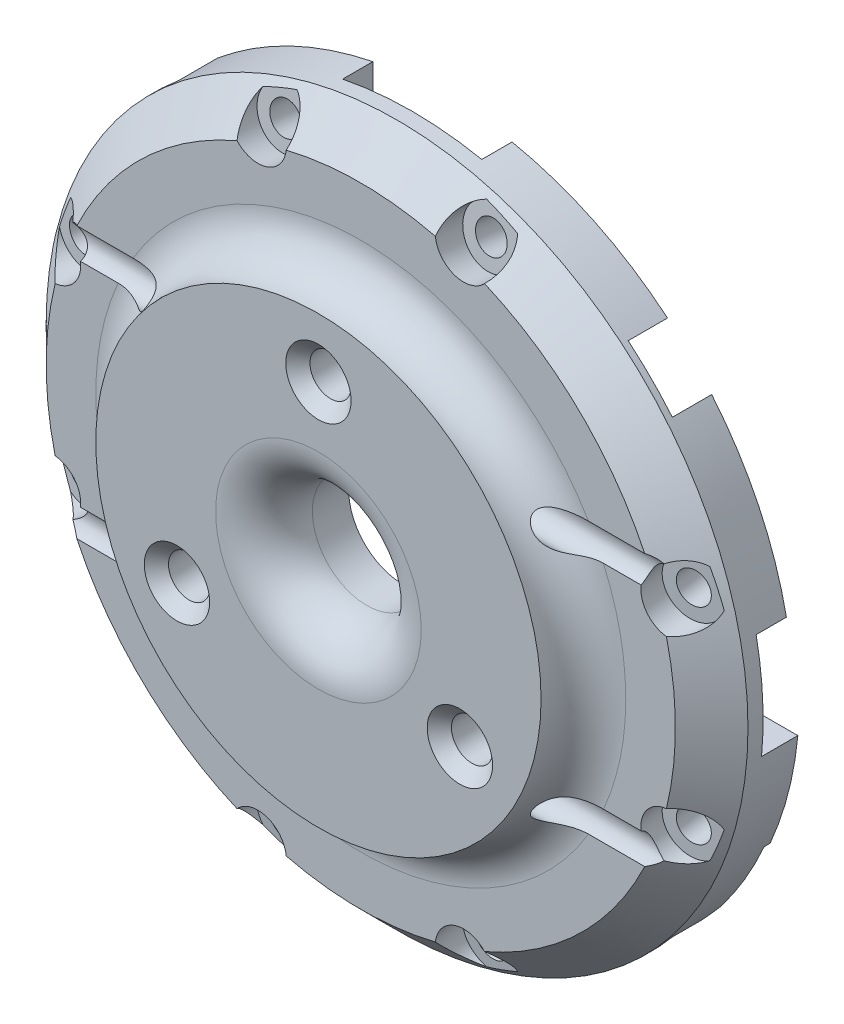
SolidWorks part; units mm, degrees
ref_plane "Front Plane" through (0, 0, 0) normal (0, 0, 1) x (1, 0, 0)
ref_plane "Top Plane" through (0, 0, 0) normal (0, 1, 0) x (1, 0, 0)
ref_plane "Right Plane" through (0, 0, 0) normal (1, 0, 0) x (0, 0, -1)
sketch "Sketch1" plane through (0, 0, 0) normal (0, 0, 1) x (1, 0, 0)
  circle A0 centre (0, 0) radius 29
  dimension "D1" = 58
extrude "Boss-Extrude1" add sketch "Sketch1" along normal blind 6.75
sketch "Sketch3" plane through (0, 0, 0) normal (0, 0, -1) x (-1, 0, 0)
  line L1 (-22.25, -22.25) -> (22.25, -22.25)
  line L2 (-22.25, -22.25) -> (-22.25, 22.25)
  line L3 (-22.25, 22.25) -> (22.25, 22.25)
  line L4 (22.25, -22.25) -> (22.25, 22.25)
  line L5 (-22.25, -22.25) -> (22.25, 22.25) construction
  line L6 (-22.25, 22.25) -> (22.25, -22.25) construction
  point P0 (0, 0)
  dimension "D1" = 44.5
extrude "Cut-Extrude1" cut sketch "Sketch3" against normal blind 3.25
sketch "Sketch4" plane through (0, 0, 6.75) normal (0, 0, 1) x (1, 0, 0)
  circle A0 centre (0, 0) radius 18.4
  dimension "D1" = 36.8
extrude "Boss-Extrude2" add sketch "Sketch4" along normal blind 3.5
fillet "Fillet1" radius 3.5 1 edges at (18.4, 0, 6.75)
sketch "Sketch5" plane through (0, 0, 10.25) normal (0, 0, 1) x (1, 0, 0)
  line L0 (-11.6913, -6.75) -> (0, 13.5) construction
  line L1 (0, 13.5) -> (11.6913, -6.75) construction
  line L2 (11.6913, -6.75) -> (-11.6913, -6.75) construction
  circle A2 centre (0, 0) radius 13.5 construction
  circle A3 centre (0, 13.5) radius 1.7
  circle A4 centre (11.6913, -6.75) radius 1.7
  circle A5 centre (-11.6913, -6.75) radius 1.7
  dimension "D1" = 3.4
  dimension "D2" = 27
extrude "Cut-Extrude2" cut sketch "Sketch5" against normal through all
sketch "Sketch7" plane through (0, 0, 3.25) normal (0, 0, -1) x (-1, 0, 0)
  circle A0 centre (-11.6913, -6.75) radius 3.25
  circle A1 centre (11.6913, -6.75) radius 3.25
  circle A2 centre (0, 13.5) radius 3.25
  dimension "D1" = 6.5
extrude "Cut-Extrude3" cut sketch "Sketch7" against normal blind 2
chamfer "Chamfer2" distance 3 angle 45 1 edges at (29, 0, 6.75)
sketch "Sketch9" plane through (0, 0, 0) normal (1, 0, 0) x (0, 0, -1)
  line L0 (-26.5723, 0) -> (15.7273, 0) construction
  line L2 (-6.75, 21.9) -> (-6.75, -21.9) construction
  circle A0 centre (-7.25, 10) radius 1.3
  circle A1 centre (-7.25, -10) radius 1.3
  dimension "D1" = 2.6
  dimension "D2" = 20
  dimension "D3" = 0.5
extrude "Cut-Extrude5" cut sketch "Sketch9" against normal through all both and the other way through all
sketch "Sketch10" plane through (0, 0, 0) normal (0, 0, -1) x (-1, 0, 0)
  line L0 (5.75, -22.0007) -> (5.75, -34.0342)
  line L1 (22.0007, 5.75) -> (34.0342, 5.75)
  line L2 (22.0007, 5.75) -> (22.0007, -5.75)
  line L3 (22.0007, -5.75) -> (34.0342, -5.75)
  line L4 (34.0342, 5.75) -> (34.0342, -5.75)
  line L5 (5.75, -22.0007) -> (-5.75, -22.0007)
  line L6 (-5.75, -22.0007) -> (-5.75, -34.0342)
  line L7 (5.75, -34.0342) -> (-5.75, -34.0342)
  line L8 (-22.0007, -5.75) -> (-34.0342, -5.75)
  line L9 (-22.0007, -5.75) -> (-22.0007, 5.75)
  line L10 (-22.0007, 5.75) -> (-34.0342, 5.75)
  line L11 (-34.0342, -5.75) -> (-34.0342, 5.75)
  line L12 (-5.75, 22.0007) -> (-5.75, 34.0342)
  line L13 (-5.75, 22.0007) -> (5.75, 22.0007)
  line L14 (5.75, 22.0007) -> (5.75, 34.0342)
  line L15 (-5.75, 34.0342) -> (5.75, 34.0342)
  point P4 (22.0007, 0)
  point P21 (0, 0)
  dimension "D1" = 11.5
  dimension "D2" = 4
extrude "Cut-Extrude6" cut sketch "Sketch10" against normal blind 2.5
sketch "Sketch13" plane through (0, 0, 3.25) normal (0, 0, -1) x (-1, 0, 0)
  line L0 (-22.25, 18.5994) -> (-22.25, -18.5994) construction
  line L1 (-22.15, 14.75) -> (-15.65, 14.75)
  line L2 (-22.15, 14.75) -> (-22.15, 8.25)
  line L3 (-22.15, 8.25) -> (-15.65, 8.25)
  line L4 (-15.65, 14.75) -> (-15.65, 8.25)
  line L5 (18.5994, 22.25) -> (-18.5994, 22.25) construction
  line L6 (14.75, 22.15) -> (14.75, 15.65)
  line L7 (14.75, 22.15) -> (8.25, 22.15)
  line L8 (8.25, 22.15) -> (8.25, 15.65)
  line L9 (14.75, 15.65) -> (8.25, 15.65)
  line L10 (22.15, -14.75) -> (15.65, -14.75)
  line L11 (22.15, -14.75) -> (22.15, -8.25)
  line L12 (22.15, -8.25) -> (15.65, -8.25)
  line L13 (15.65, -14.75) -> (15.65, -8.25)
  line L14 (-14.75, -22.15) -> (-14.75, -15.65)
  line L15 (-14.75, -22.15) -> (-8.25, -22.15)
  line L16 (-8.25, -22.15) -> (-8.25, -15.65)
  line L17 (-14.75, -15.65) -> (-8.25, -15.65)
  point P23 (0, 0)
  dimension "D1" = 0.1
  dimension "D2" = 7.5
  dimension "D4" = 6.5
  dimension "D3" = 4
extrude "Cut-Extrude9" cut sketch "Sketch13" against normal blind 2.25
chamfer "Chamfer5" distance 1 angle 45 12 edges at (-14.75, 18.9, 3.25) (-11.5, 15.65, 3.25) (-8.25, 18.9, 3.25) (14.75, -18.9, 3.25) (11.5, -15.65, 3.25) (8.25, -18.9, 3.25) (-18.9, -8.25, 3.25) (-15.65, -11.5, 3.25) (-18.9, -14.75, 3.25) (18.9, 8.25, 3.25) (15.65, 11.5, 3.25) (18.9, 14.75, 3.25)
sketch "Sketch14" plane through (0, 0, 0) normal (0, 0, -1) x (-1, 0, 0)
  line L1 (-35.1198, 0) -> (-19.2322, 0)
  line L2 (-35.1198, 0) -> (-35.1198, -11.6)
  line L3 (-35.1198, -11.6) -> (-19.2322, -11.6)
  line L4 (-19.2322, 0) -> (-19.2322, -11.6)
  dimension "D1" = 11.6
extrude "Cut-Extrude10" cut sketch "Sketch14" against normal up to surface (2.5 mm away) up to face at (25.4811, 0, 2.5)
fillet "Fillet2" radius 1.5 3 edges at (-8.5776, -5.8189, 3.25) (8.4413, -6.75, 3.25) (-3.25, 13.5, 3.25)
sketch "Sketch15" plane through (0, 0, 6.75) normal (0, 0, 1) x (1, 0, 0)
  line L0 (0, 0) -> (11.6673, 11.6673) construction
  line L1 (0, 0) -> (36.7921, 0) construction
  circle A0 centre (11.6673, 11.6673) radius 12.5
  circle A1 centre (0, 0) radius 29 construction
  dimension "D2" = 25
  dimension "D1" = 45
sketch "Sketch19" plane through (0, 0, 2.5) normal (0, 0, -1) x (-1, 0, 0)
  line L0 (-22.25, -2.75) -> (-22.25, -11.6)
  line L1 (-22.25, -11.6) -> (-22.25, 5.75) construction
  line L2 (-22.25, -11.6) -> (-26.5789, -11.6)
  line L3 (-22.25, -2.75) -> (-28.8693, -2.75)
  line L4 (-22.25, 5.75) -> (-28.4242, 5.75) construction
  arc A0 (-28.8693, -2.75) -> (-26.5789, -11.6) centre (0, 0) ccw
  arc A1 (-28.4242, 5.75) -> (-26.5789, -11.6) centre (0, 0) ccw construction
  dimension "D1" = 8.5
extrude "Boss-Extrude3" add sketch "Sketch19" along normal blind 3
chamfer "Chamfer7" distance 1.25 angle 45 1 edges at (22.25, -7.175, -0.5)
sketch "Sketch16" plane through (0, 0, 10.25) normal (0, 0, 1) x (1, 0, 0)
  circle A0 centre (0, 0) radius 4.5
  dimension "D1" = 9
extrude "Cut-Extrude11" cut sketch "Sketch16" against normal through all
fillet "Fillet3" radius 4 1 edges at (4.5, 0, 10.25)
chamfer "Chamfer6" distance 1 angle 45 3 edges at (13.3913, -6.75, 10.25) (-9.9913, -6.75, 10.25) (1.7, 13.5, 10.25)
ref_axis "Axis1" through (0, 0, -0.4875) along (0, 0, 1)
ref_axis "Axis2" through (0, 31.9, 0) along (0, -1, 0)
ref_plane "Plane1" through (0, 0, 0) normal (0.1219, 0, 0.9925) x (0, -1, 0)
sketch "Sketch17" plane through (0, 0, 0) normal (0.1219, 0, 0.9925) x (0, -1, 0)
  line L0 (0, 0) -> (0, 33.2124) construction
  line L1 (0, 0.0594) -> (0, -1.2476) construction
  circle A0 centre (-8.5, 24.5) radius 1.3
  circle A1 centre (8.5, 24.5) radius 1.3
  dimension "D1" = 2.6
  dimension "D2" = 17
  dimension "D3" = 24.5
extrude "Cut-Extrude12" cut sketch "Sketch17" along normal through all
sketch "Sketch18" plane through (0, 0, 0) normal (0.1219, 0, 0.9925) x (0, -1, 0)
  circle A0 centre (-8.5, 24.5) radius 2.35
  circle A1 centre (8.5, 24.5) radius 2.35
  dimension "D1" = 4.7
extrude "Cut-Extrude13" cut sketch "Sketch18" against normal blind 12.5 from offset 20
pattern_circular "CirPattern1" count 4 over 360 about axis through (0, 0, -0.4875) along (0, 0, 1) of "Cut-Extrude12", "Cut-Extrude13"
